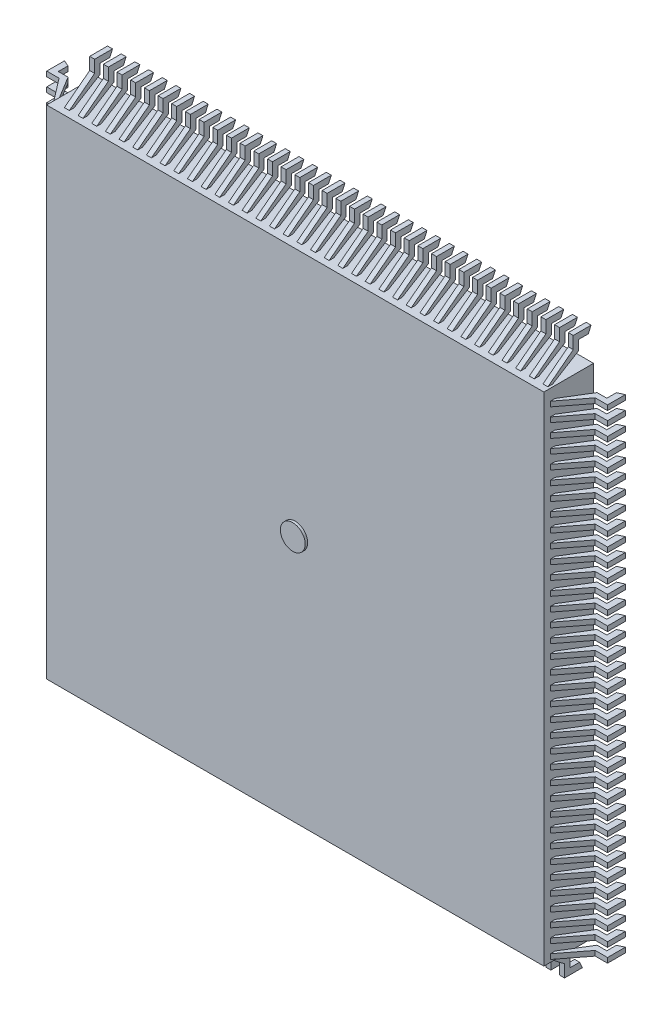
SolidWorks part; units mm, degrees
ref_plane "前视基准面" through (0, 0, 0) normal (0, 0, 1) x (1, 0, 0)
ref_plane "上视基准面" through (0, 0, 0) normal (0, 1, 0) x (1, 0, 0)
ref_plane "右视基准面" through (0, 0, 0) normal (1, 0, 0) x (0, 0, -1)
sketch "草图1" plane through (0, 0, 0) normal (0, 0, 1) x (1, 0, 0)
  line L1 (0, 0) -> (20, 0)
  line L2 (0, 0) -> (0, -20)
  line L3 (0, -20) -> (20, -20)
  line L4 (20, 0) -> (20, -20)
  dimension "D1" = 20
  dimension "D2" = 20
extrude "凸台-拉伸1" add sketch "草图1" along normal blind 2
ref_plane "基准面1" through (0.1, 0, 0) normal (-1, 0, 0) x (0, 0, 1)
sketch "草图2" plane through (0.1, 0, 0) normal (-1, 0, 0) x (0, 0, 1)
  line L0 (1.7358, -20) -> (0.7176, -20.7847)
  line L1 (2, -20) -> (0, -20) construction
  line L2 (0.7176, -20.7847) -> (0.7176, -21.2792)
  line L3 (0.7176, -21.2792) -> (0, -21.2792)
  line L7 (0.1129, -21.0319) -> (0.4994, -21.0319)
  line L8 (0.4994, -21.0319) -> (0.4994, -20.6396)
  line L9 (0.4994, -20.6396) -> (1.5467, -20)
  line L10 (1.5467, -20) -> (1.7358, -20)
  line L11 (0.1129, -21.0319) -> (0, -21.2792)
extrude "凸台-拉伸2" add sketch "草图2" against normal blind 0.2
pattern_linear "阵列(线性)1" count 36 spacing 0.55 along (1, 0, 0) of "凸台-拉伸2"
sketch "草图3" plane through (0, 0, 2) normal (0, 0, 1) x (1, 0, 0)
  line L0 (21.5316, -10) -> (-4.1261, -10) construction
  line L1 (10, 2.4037) -> (10, -13.5814) construction
  circle A0 centre (10, -10) radius 0.5
  dimension "D1" = 1
extrude "凸台-拉伸3" add sketch "草图3" along normal blind 0.1
ref_axis "基准轴1" through (10, -10, 13.2889) along (0, 0, -1)
pattern_circular "阵列(圆周)1" count 4 every 90 about axis through (10, -10, 13.2889) along (0, 0, -1) of "阵列(线性)1", "凸台-拉伸2"
